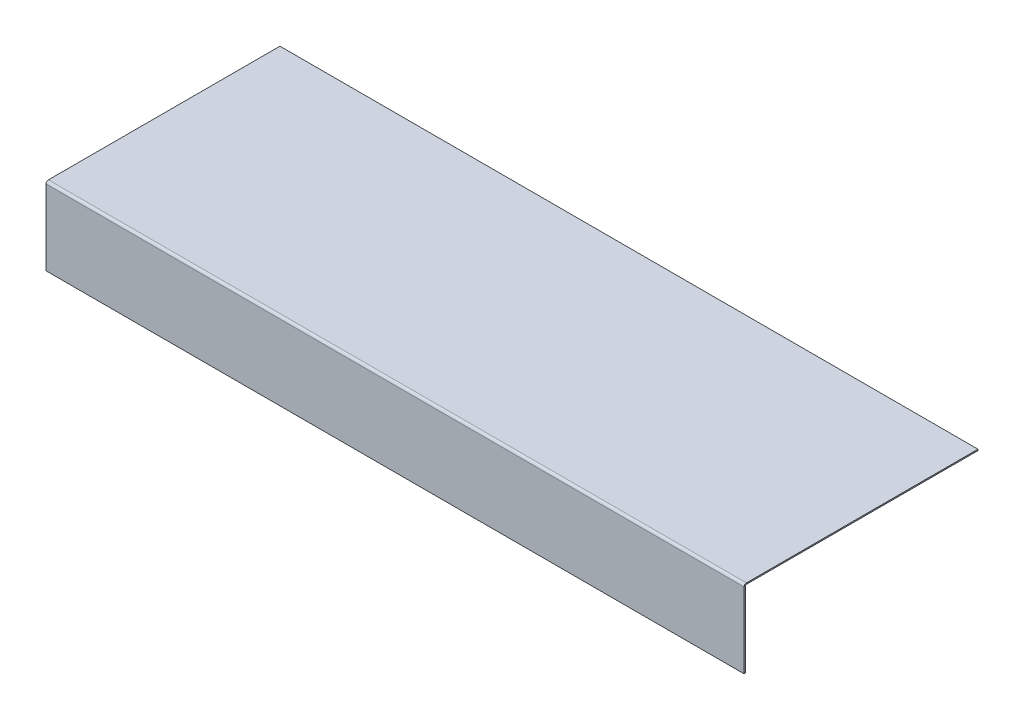
SolidWorks part; units mm, degrees
note: The reader was unsure of these and kept them because the rebuilt part matched: flange length of "Edge-Flange1".
ref_plane "Front Plane" through (0, 0, 0) normal (0, 0, 1) x (1, 0, 0)
ref_plane "Top Plane" through (0, 0, 0) normal (0, 1, 0) x (1, 0, 0)
ref_plane "Right Plane" through (0, 0, 0) normal (1, 0, 0) x (0, 0, -1)
sketch "Sketch1" plane through (0, 0, 0) normal (0, 1, 0) x (1, 0, 0)
  line L1 (-228.6, 0) -> (228.6, 0)
  line L2 (-228.6, 0) -> (-228.6, -152.4)
  line L3 (-228.6, -152.4) -> (228.6, -152.4)
  line L4 (228.6, 0) -> (228.6, -152.4)
  dimension "D1" = 457.2
  dimension "D2" = 152.4
base flange "Base-Flange1" sketch "Sketch1" thickness 0.8128 reverse thickness direction no parameters "D1"=0.7366
edge flange "Edge-Flange1" sketch "Sketch8" flange angle 90 flange length 50.8 flange position material outside bend radius 0.7366 thickness 0.8128 relief rectangular parameters "D6"=10
sketch "Sketch8" plane through (0, -0.8128, 152.4) normal (0, 0, 1) x (-1, 0, 0)
  line L2 (-228.6, 0) -> (-228.6, 49.9872)
  line L3 (-228.6, 49.9872) -> (228.6, 49.9872)
  line L4 (228.6, 49.9872) -> (228.6, 0)
  line L5 (228.6, 0) -> (-228.6, 0) construction
  line L6 (228.6, 0) -> (-228.6, 0)
bend "EdgeBend1" bend radius 0.7366 bend angle 90 parameters "D5"=1
sketch "Bend-Lines1" plane through (0, 0, 0) normal (0, 1, 0) x (1, 0, 0)
sketch "Bounding-Box1" plane through (0, 0, 0) normal (0, 1, 0) x (1, 0, 0)
sheet metal parameters "Sheet-Metal1" thickness 0.8128 parameters "D1"=0.7366
flat pattern "Flat-Pattern1" [suppressed]
sketch "Bend-Lines2" plane through (0, 0, 0) normal (0, 1, 0) x (1, 0, 0)
sketch "Bounding-Box2" [suppressed] plane through (0, 0, 0) normal (0, 1, 0) x (1, 0, 0)
sheet metal parameters "Sheet-Metal2" thickness 0.8128 parameters "D1"=0.7366
flat pattern "Flat-Pattern1" [suppressed]
sketch "Bend-Lines2" plane through (0, 0, 0) normal (0, 1, 0) x (1, 0, 0)
sketch "Bounding-Box2" [suppressed] plane through (0, 0, 0) normal (0, 1, 0) x (1, 0, 0)
bend of the flat pattern "Flatten-<EdgeBend1>1"
